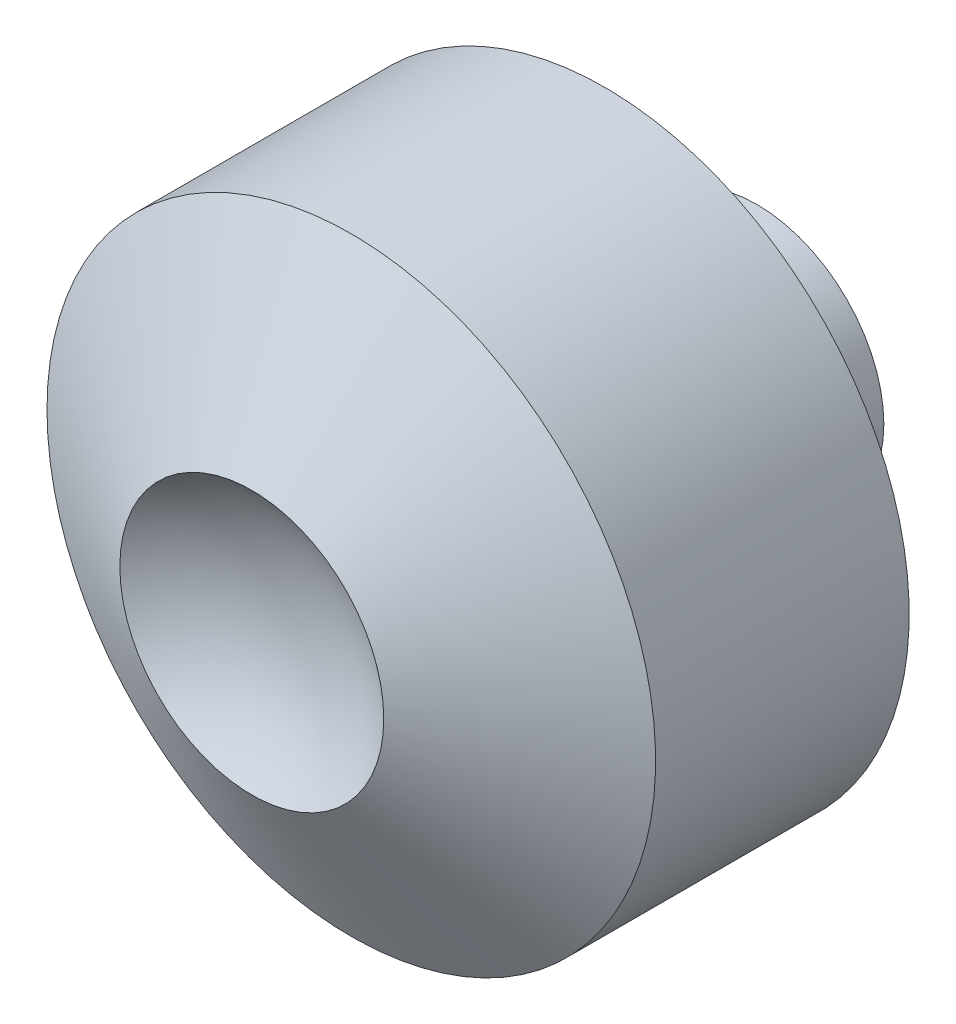
SolidWorks part; units mm, degrees
ref_plane "Front Plane" through (0, 0, 0) normal (0, 0, 1) x (1, 0, 0)
ref_plane "Top Plane" through (0, 0, 0) normal (0, 1, 0) x (1, 0, 0)
ref_plane "Right Plane" through (0, 0, 0) normal (1, 0, 0) x (0, 0, -1)
sketch "Sketch2" plane through (0, 0, 0) normal (0, 0, 1) x (1, 0, 0)
  circle A0 centre (0, 0) radius 6
  dimension "D1" = 12
extrude "Boss-Extrude1" add sketch "Sketch2" along normal blind 2 contours A0
sketch "Sketch3" plane through (0, 0, 0) normal (1, 0, 0) x (0, 0, -1)
  line L0 (-2, 0) -> (-5, 0) construction
  line L1 (-2, 6) -> (-2, -6) construction
  line L2 (-5, 4) -> (-5, -4)
  circle A0 centre (-5, 0) radius 4
  dimension "D2" = 8
  dimension "D1" = 3
revolve "Cut-Revolve1" cut sketch "Sketch3" angle 360 about L2 region at (0, 0, 3.3023)
chamfer "Chamfer1" distance 2 angle 60 1 edges at (6, 0, 2) first distance on face at (6, 0, 2)
sketch "Sketch4" plane through (0, 0, 0) normal (0, 0, -1) x (-1, 0, 0)
  circle A0 centre (0, 0) radius 6
  dimension "D1" = 12
extrude "Boss-Extrude2" add sketch "Sketch4" along normal blind 5
sketch "Sketch6" plane through (0, 0, -5) normal (0, 0, -1) x (-1, 0, 0)
  circle A0 centre (0, 0) radius 2.5
  dimension "D1" = 5
extrude "Boss-Extrude3" add sketch "Sketch6" along normal blind 3
